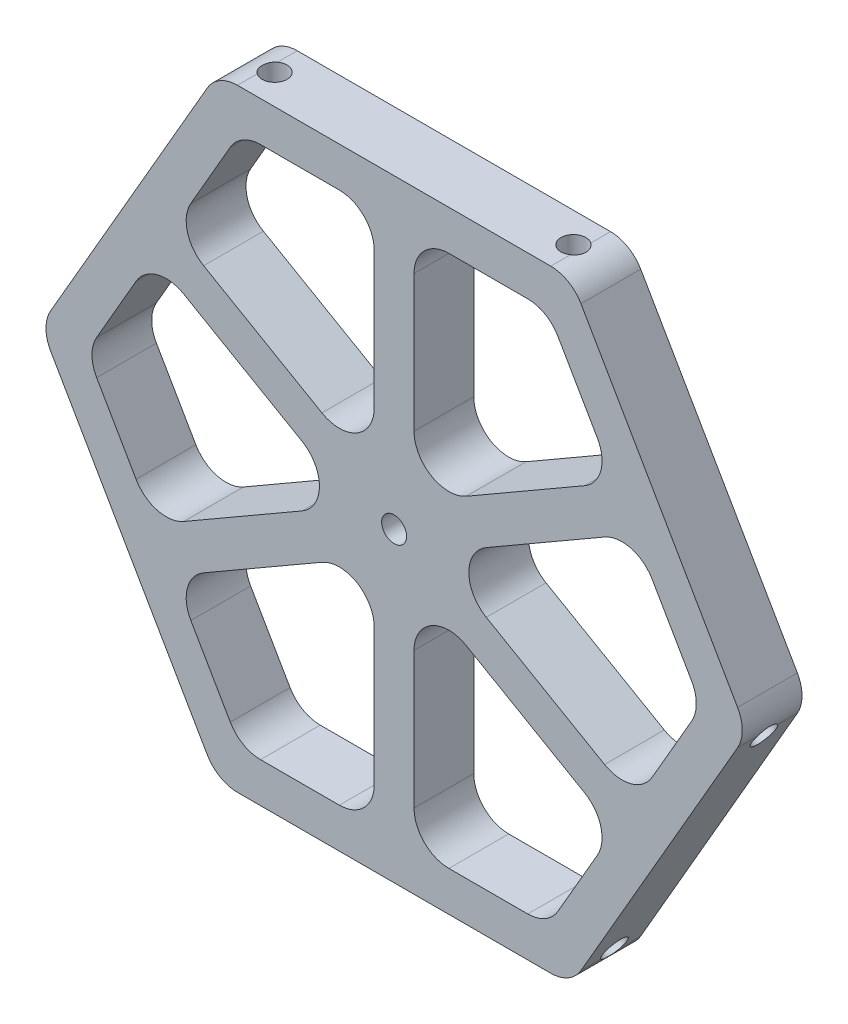
SolidWorks part; units mm, degrees
ref_plane "Front Plane" through (0, 0, 0) normal (0, 0, 1) x (1, 0, 0)
ref_plane "Top Plane" through (0, 0, 0) normal (0, 1, 0) x (1, 0, 0)
ref_plane "Right Plane" through (0, 0, 0) normal (1, 0, 0) x (0, 0, -1)
sketch "Sketch1" plane through (0, 0, 0) normal (0, 0, 1) x (1, 0, 0)
  line L0 (0, -30.7387) -> (17.747, -30.7387)
  line L1 (26.6205, -15.3694) -> (17.747, -30.7387)
  line L2 (-2, 3.4641) -> (-2, 26.7387)
  line L3 (-4, 0) -> (-24.1564, -11.6373)
  line L4 (-2, 3.4641) -> (-22.1564, 15.1014)
  line L9 (26.6205, -15.3694) -> (35.494, 0)
  line L10 (2, 3.4641) -> (22.1564, 15.1014)
  line L15 (26.6205, 15.3694) -> (35.494, 0)
  line L16 (4, 0) -> (24.1564, -11.6373)
  line L21 (-2, -3.4641) -> (-2, -26.7387)
  line L22 (2, -3.4641) -> (2, -26.7387)
  line L27 (26.6205, 15.3694) -> (17.747, 30.7387)
  line L28 (-2, -3.4641) -> (-22.1564, -15.1014)
  line L33 (0, 30.7387) -> (17.747, 30.7387)
  line L34 (-4, 0) -> (-24.1564, 11.6373)
  line L39 (2, 3.4641) -> (2, 26.7387)
  line L40 (4, 0) -> (24.1564, 11.6373)
  line L41 (2, -3.4641) -> (22.1564, -15.1014)
  line L42 (0, 30.7387) -> (-17.747, 30.7387)
  line L43 (-26.6205, 15.3694) -> (-17.747, 30.7387)
  line L44 (-26.6205, 15.3694) -> (-35.494, 0)
  line L45 (-26.6205, -15.3694) -> (-35.494, 0)
  line L46 (-26.6205, -15.3694) -> (-17.747, -30.7387)
  line L47 (0, -30.7387) -> (-17.747, -30.7387)
  line L48 (-24.1564, -11.6373) -> (-30.8752, 0)
  line L49 (-24.1564, 11.6373) -> (-30.8752, 0)
  line L50 (-6, 0) -> (-24.6564, 10.7713)
  line L51 (-6, 0) -> (-24.6564, -10.7713)
  line L52 (-22.1564, -15.1014) -> (-15.4376, -26.7387)
  line L53 (-2, -26.7387) -> (-15.4376, -26.7387)
  line L54 (-3, -5.1962) -> (-3, -26.7387)
  line L55 (-3, -5.1962) -> (-21.6564, -15.9674)
  line L56 (2, -26.7387) -> (15.4376, -26.7387)
  line L57 (22.1564, -15.1014) -> (15.4376, -26.7387)
  line L58 (3, -5.1962) -> (21.6564, -15.9674)
  line L59 (3, -5.1962) -> (3, -26.7387)
  line L60 (6, 0) -> (24.6564, -10.7713)
  line L61 (24.1564, -11.6373) -> (30.8752, 0)
  line L62 (24.1564, 11.6373) -> (30.8752, 0)
  line L63 (6, 0) -> (24.6564, 10.7713)
  line L64 (22.1564, 15.1014) -> (15.4376, 26.7387)
  line L65 (2, 26.7387) -> (15.4376, 26.7387)
  line L66 (3, 5.1962) -> (3, 26.7387)
  line L67 (3, 5.1962) -> (21.6564, 15.9674)
  line L68 (-22.1564, 15.1014) -> (-15.4376, 26.7387)
  line L69 (-2, 26.7387) -> (-15.4376, 26.7387)
  line L70 (-3, 5.1962) -> (-3, 26.7387)
  line L71 (-3, 5.1962) -> (-21.6564, 15.9674)
  line L72 (-3, 26.7387) -> (-15.4376, 26.7387) construction
  line L73 (-21.6564, 15.9674) -> (-15.4376, 26.7387) construction
  line L74 (-24.6564, 10.7713) -> (-30.8752, 0) construction
  line L75 (-24.6564, -10.7713) -> (-30.8752, 0) construction
  line L76 (21.6564, 15.9674) -> (15.4376, 26.7387) construction
  line L77 (3, 26.7387) -> (15.4376, 26.7387) construction
  line L78 (24.6564, 10.7713) -> (30.8752, 0) construction
  line L79 (24.6564, -10.7713) -> (30.8752, 0) construction
  line L80 (21.6564, -15.9674) -> (15.4376, -26.7387) construction
  line L81 (3, -26.7387) -> (15.4376, -26.7387) construction
  line L82 (-3, -26.7387) -> (-15.4376, -26.7387) construction
  line L83 (-21.6564, -15.9674) -> (-15.4376, -26.7387) construction
  line L84 (3, -5.1962) -> (21.6564, -15.9674) construction
  line L85 (3, -5.1962) -> (3, -26.7387) construction
  line L86 (-3, -5.1962) -> (-3, -26.7387) construction
  line L87 (-3, -5.1962) -> (-21.6564, -15.9674) construction
  line L88 (-6, 0) -> (-24.6564, -10.7713) construction
  line L89 (-6, 0) -> (-24.6564, 10.7713) construction
  line L90 (-3, 5.1962) -> (-21.6564, 15.9674) construction
  line L91 (-3, 5.1962) -> (-3, 26.7387) construction
  line L92 (3, 5.1962) -> (3, 26.7387) construction
  line L93 (3, 5.1962) -> (21.6564, 15.9674) construction
  line L94 (6, 0) -> (24.6564, 10.7713) construction
  line L95 (6, 0) -> (24.6564, -10.7713) construction
  line L96 (-2, -27.7387) -> (-16.015, -27.7387) construction
  line L97 (-23.0224, -15.6014) -> (-16.015, -27.7387) construction
  line L98 (-2, -3.4641) -> (-23.0224, -15.6014) construction
  line L101 (-2, -3.4641) -> (-2, -27.7387) construction
  line L102 (2, -27.7387) -> (16.015, -27.7387) construction
  line L103 (2, -3.4641) -> (2, -27.7387) construction
  line L105 (23.0224, -15.6014) -> (16.015, -27.7387) construction
  line L107 (2, -3.4641) -> (23.0224, -15.6014) construction
  line L108 (4, 0) -> (25.0224, -12.1373) construction
  line L109 (25.0224, -12.1373) -> (32.0299, 0) construction
  line L111 (25.0224, 12.1373) -> (32.0299, 0) construction
  line L113 (4, 0) -> (25.0224, 12.1373) construction
  line L114 (2, 3.4641) -> (23.0224, 15.6014) construction
  line L115 (23.0224, 15.6014) -> (16.015, 27.7387) construction
  line L117 (2, 27.7387) -> (16.015, 27.7387) construction
  line L118 (2, 3.4641) -> (2, 27.7387) construction
  line L119 (-2, 27.7387) -> (-16.015, 27.7387) construction
  line L120 (-2, 3.4641) -> (-2, 27.7387) construction
  line L121 (-23.0224, 15.6014) -> (-16.015, 27.7387) construction
  line L122 (-2, 3.4641) -> (-23.0224, 15.6014) construction
  line L123 (-4, 0) -> (-25.0224, 12.1373) construction
  line L124 (-25.0224, 12.1373) -> (-32.0299, 0) construction
  line L125 (-25.0224, -12.1373) -> (-32.0299, 0) construction
  line L126 (-4, 0) -> (-25.0224, -12.1373) construction
  circle A0 centre (0, 0) radius 1.25
  point P81 (0, 0)
  dimension "D4" = 1
  dimension "D2" = 1
  dimension "D3" = 1
  dimension "D5" = 1
  dimension "D7" = 1
  dimension "D8" = 1
  dimension "D6" = 6
extrude "Boss-Extrude4" add sketch "Sketch1" along normal blind 6 contours L47 L0 L1 L9 L15 L27 L33 L42 L43 L44 L45 L46 A0 L69 L2 L4 L68 L49 L34 L3 L48 L21 L53 L52 L28 L41 L57 L56 L22 L40 L62 L61 L16 L39
fillet "Fillet1" radius 3.5 30 edges at (-2, 3.4641, 3) (2, 3.4641, 3) (4, 0, 3) (2, -3.4641, 3) (-2, -3.4641, 3) (-4, 0, 3) (2, 26.7387, 3) (15.4376, 26.7387, 3) (22.1564, 15.1014, 3) (24.1564, 11.6373, 3) (30.8752, 0, 3) (24.1564, -11.6373, 3) (22.1564, -15.1014, 3) (15.4376, -26.7387, 3) (2, -26.7387, 3) (-2, -26.7387, 3) (-15.4376, -26.7387, 3) (-22.1564, -15.1014, 3) (-24.1564, -11.6373, 3) (-30.8752, 0, 3) (-24.1564, 11.6373, 3) (-22.1564, 15.1014, 3) (-15.4376, 26.7387, 3) (-2, 26.7387, 3) (-35.494, 0, 3) (-17.747, 30.7387, 3) (17.747, 30.7387, 3) (35.494, 0, 3) (17.747, -30.7387, 3) (-17.747, -30.7387, 3)
sketch "Sketch2" plane through (-26.6205, -15.3694, 0) normal (-0.866, -0.5, 0) x (0, 0, 1)
  line L0 (0, 0) -> (6, 0) construction
  line L1 (6, -15.7263) -> (6, 15.7263) construction
  line L2 (3, 0) -> (3, 15) construction
  line L3 (3, 0) -> (3, -15) construction
  circle A0 centre (3, 15) radius 1.25
  circle A1 centre (3, -15) radius 1.25
extrude "Cut-Extrude1" cut sketch "Sketch2" against normal blind 3
pattern_circular "CirPattern1" count 3 every 120 about axis through (0, 0, 6) along (0, 0, 1) of "Cut-Extrude1"
sketch "Sketch3" plane through (0, 0, 0) normal (0, 0, -1) x (-1, 0, 0)
  circle A0 centre (0, 0) radius 1.25
extrude "Boss-Extrude5" add sketch "Sketch3" against normal blind 1
